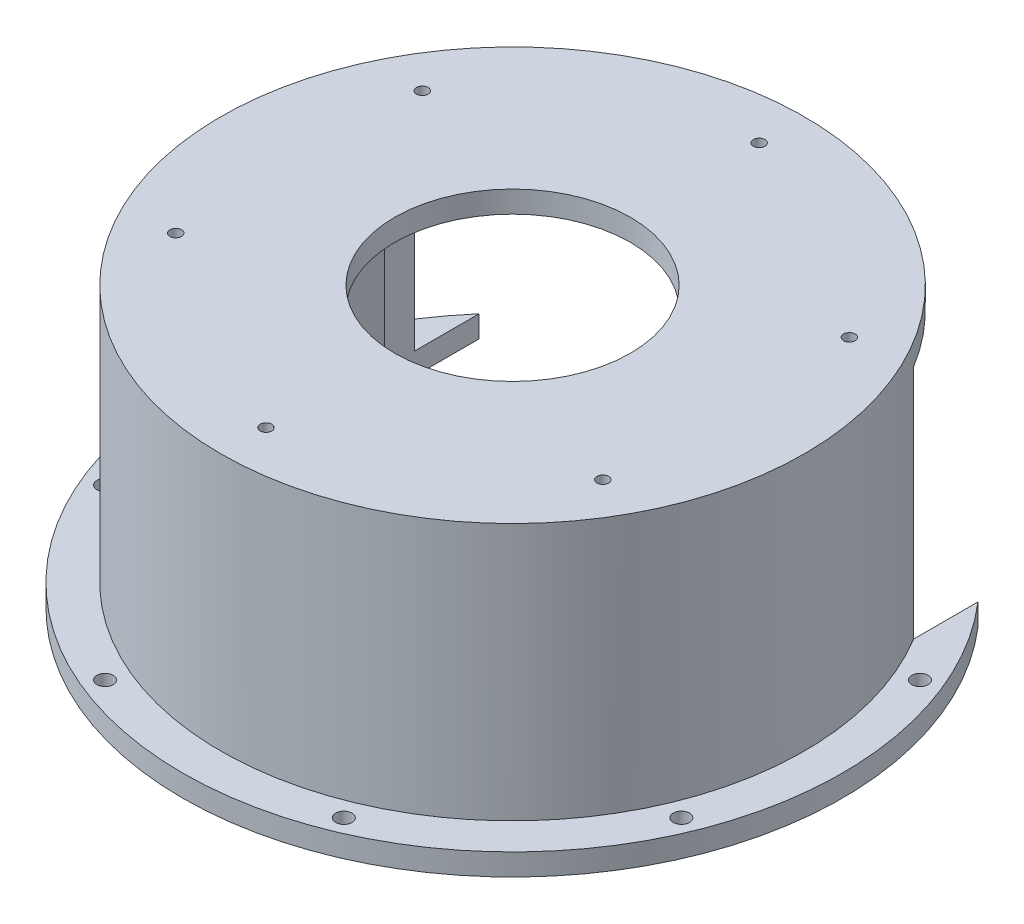
SolidWorks part; units mm, degrees
ref_plane "Front Plane" through (0, 0, 0) normal (0, 0, 1) x (1, 0, 0)
ref_plane "Top Plane" through (0, 0, 0) normal (0, 1, 0) x (1, 0, 0)
ref_plane "Right Plane" through (0, 0, 0) normal (1, 0, 0) x (0, 0, -1)
sketch "Sketch1" plane through (0, 0, 0) normal (0, 1, 0) x (1, 0, 0)
  circle A0 centre (0, 0) radius 144.4625
  dimension "D1" = 288.925
extrude "Boss-Extrude1" add sketch "Sketch1" along normal blind 9.525
sketch "Sketch2" plane through (0, 9.525, 0) normal (0, 1, 0) x (1, 0, 0)
  line L0 (0, 0) -> (-52.2459, 126.1327) construction
  line L2 (0, -5.2388) -> (0, 5.2388) construction
  circle A0 centre (0, 0) radius 136.525
  point P3 (-52.2459, 126.1327)
  point P4 (52.2459, 126.1327)
  point P5 (126.1327, 52.2459)
  point P8 (126.1327, -52.2459)
  point P9 (52.2459, -126.1327)
  point P10 (-52.2459, -126.1327)
  point P11 (-126.1327, -52.2459)
  point P12 (-126.1327, 52.2459)
  point P22 (0, 136.525)
  point P25 (1.5165, 136.5166)
  dimension "D1" = 273.05
  dimension "D3" = 22.5
  dimension "D4" = 22.5
  dimension "D2" = 8
hole_wizard "1/4 Clearance Hole1" positions "Sketch2" profile "Sketch3" hole size "1/4" standard "ANSI Inch" end condition up to next
sketch "Sketch3" plane through (0, 9.525, -136.525) normal (1, 0, 0) x (0, 0, 1)
  line L0 (0, 0) -> (0, 9.525)
  line L1 (0, 9.525) -> (3.5712, 9.525)
  line L2 (3.5712, 9.525) -> (3.5712, 0)
  line L5 (3.5712, 0) -> (0, 0)
  line L11 (0, -6.35) -> (0, 107.95) construction
  dimension "Thru Hole Dia." = 7.1425
  dimension "Thru Hole Depth" = 9.525
sketch "Sketch4" plane through (0, 9.525, 0) normal (0, 1, 0) x (1, 0, 0)
  circle A0 centre (0, 0) radius 127.7937
  circle A1 centre (0, 0) radius 121.4438
  dimension "D1" = 255.5875
  dimension "D2" = 242.8875
extrude "Boss-Extrude2" add sketch "Sketch4" along normal blind 112.7125
sketch "Sketch5" plane through (0, 122.2375, 0) normal (0, 1, 0) x (1, 0, 0)
  circle A0 centre (0, 0) radius 121.4438 construction
  circle A1 centre (0, 0) radius 127.7937
  circle A2 centre (0, 0) radius 127.7937
  circle A3 centre (0, 0) radius 121.4438
  dimension "D1" = 0
extrude "Boss-Extrude3" add sketch "Sketch5" against normal blind 9.525 contours A3
sketch "Sketch6" plane through (0, 0, 0) normal (0, -1, 0) x (1, 0, 0)
  circle A0 centre (0, 0) radius 121.4438
  dimension "D1" = 242.8875
extrude "Cut-Extrude1" cut sketch "Sketch6" against normal up to next
sketch "Sketch7" plane through (0, 122.2375, 0) normal (0, 1, 0) x (1, 0, 0)
  circle A0 centre (0, 0) radius 51.5938
  dimension "D1" = 103.1875
extrude "Cut-Extrude2" cut sketch "Sketch7" against normal up to next
sketch "Sketch10" plane through (0, 0, 0) normal (0, 1, 0) x (1, 0, 0)
  line L0 (-109.22, 53.0997) -> (109.22, 53.0997)
  line L1 (-109.22, 53.0997) -> (-109.22, 144.4625)
  line L2 (109.22, 53.0997) -> (109.22, 144.4625)
  line L3 (-109.22, 144.4625) -> (109.22, 144.4625)
  circle A0 centre (0, 0) radius 121.4438 construction
  circle A1 centre (0, 0) radius 144.4625 construction
  point P6 (0, 144.4625)
  point P7 (0, 0)
  dimension "D1" = 218.44
extrude "Cut-Extrude3" cut sketch "Sketch10" along normal up to surface (112.7125 mm away) contours L1 L3 L2 L0 up to face at (0, 112.7125, 51.5938)
sketch "Sketch11" plane through (0, 122.2375, 0) normal (0, 1, 0) x (1, 0, 0)
  circle A0 centre (0, 0) radius 107.95
  point P3 (0, -107.95)
  point P4 (-93.4874, -53.975)
  point P7 (-93.4874, 53.975)
  point P8 (0, 107.95)
  point P9 (93.4874, 53.975)
  point P10 (93.4874, -53.975)
  dimension "D1" = 215.9
  dimension "D2" = 6
hole_wizard "Tap Drill for 1/4-20 Tap1" positions "Sketch11" profile "Sketch12" hole size "1/4-20" standard "ANSI Inch" end condition up to next
sketch "Sketch12" plane through (93.4874, 122.2375, 53.975) normal (1, 0, 0) x (0, 0, 1)
  line L0 (0, 0) -> (0, 9.525)
  line L1 (0, 9.525) -> (2.5527, 9.525)
  line L2 (2.5527, 9.525) -> (2.5527, 0)
  line L5 (2.5527, 0) -> (0, 0)
  line L11 (0, -6.35) -> (0, 107.95) construction
  dimension "Thru Hole Dia." = 5.1054
  dimension "Thru Hole Depth" = 9.525
